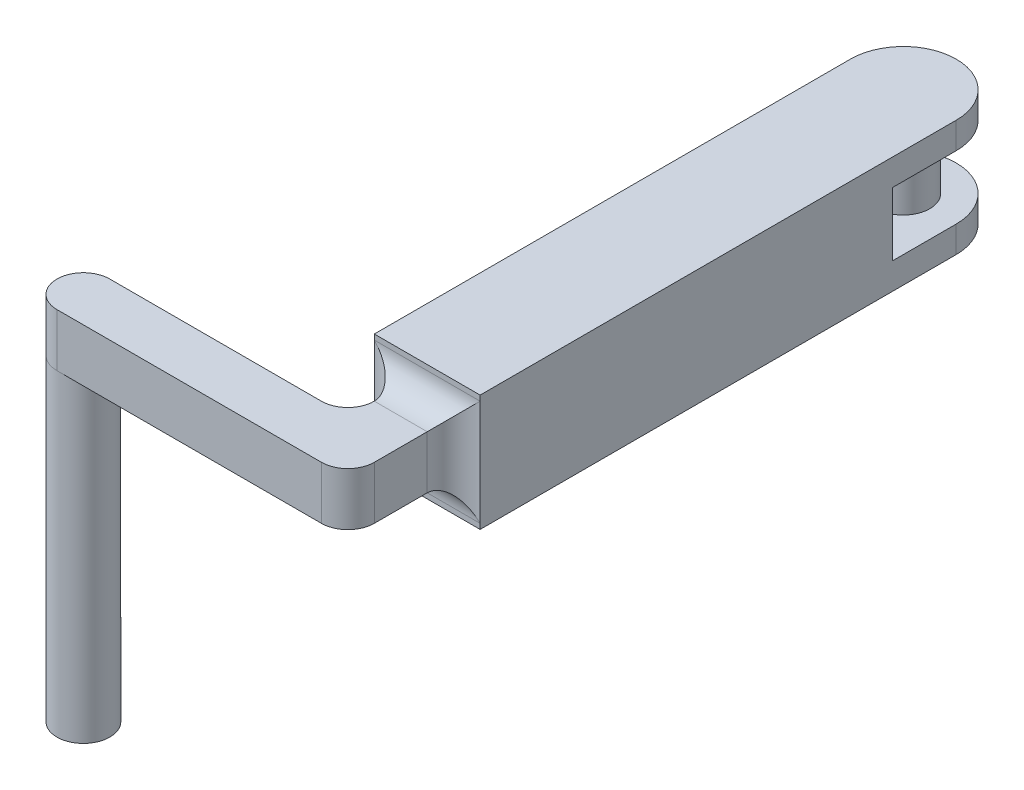
SolidWorks part; units mm, degrees
ref_plane "Front Plane" through (0, 0, 0) normal (0, 0, 1) x (1, 0, 0)
ref_plane "Top Plane" through (0, 0, 0) normal (0, 1, 0) x (1, 0, 0)
ref_plane "Right Plane" through (0, 0, 0) normal (1, 0, 0) x (0, 0, -1)
sketch "Sketch1" plane through (0, 0, 0) normal (0, 1, 0) x (1, 0, 0)
  circle A0 centre (0, 0) radius 3.175
  dimension "D1" = 6.35
extrude "Boss-Extrude1" add sketch "Sketch1" against normal blind 38.1
sketch "Sketch2" plane through (0, 0, 0) normal (0, 1, 0) x (1, 0, 0)
  line L0 (0, 0) -> (0, 3.175) construction
  line L1 (34.925, 3.175) -> (-3.175, 3.175) construction
  line L2 (34.925, 3.175) -> (34.925, -3.175) construction
  line L3 (34.925, -3.175) -> (-3.175, -3.175)
  line L4 (-3.175, 3.175) -> (-3.175, -3.175)
  line L5 (34.925, 3.175) -> (-3.175, -3.175) construction
  line L6 (34.925, -3.175) -> (-3.175, 3.175) construction
  line L7 (0, 0) -> (-3.175, 0) construction
  line L8 (-3.175, 3.175) -> (28.575, 3.175)
  line L9 (28.575, 3.175) -> (28.575, 60.325)
  line L10 (28.575, 60.325) -> (34.925, 60.325)
  line L11 (34.925, 60.325) -> (34.925, -3.175)
  point P0 (15.875, 0)
  dimension "D1" = 6.35
  dimension "D2" = 38.1
  dimension "D3" = 6.35
  dimension "D4" = 63.5
extrude "Boss-Extrude2" add sketch "Sketch2" along normal blind 6.35
fillet "Fillet1" radius 3.175 4 edges at (28.575, 3.175, -3.175) (34.925, 3.175, 3.175) (-3.175, 3.175, -3.175) (-3.175, 3.175, 3.175)
sketch "Sketch3" plane through (0, 6.35, 0) normal (0, 1, 0) x (1, 0, 0)
  line L0 (25.4, 41.275) -> (31.75, 41.275) construction
  line L1 (25.4, 9.525) -> (38.1, 9.525)
  line L2 (25.4, 9.525) -> (25.4, 73.025)
  line L3 (25.4, 73.025) -> (38.1, 73.025)
  line L4 (38.1, 9.525) -> (38.1, 73.025)
  line L5 (31.75, 41.275) -> (31.75, 73.025) construction
  line L6 (34.925, 60.325) -> (28.575, 60.325) construction
  line L7 (0, -3.175) -> (31.75, -3.175) construction
  point P9 (31.75, 60.325)
  dimension "D1" = 12.7
  dimension "D2" = 12.7
  dimension "D3" = 63.5
extrude "Boss-Extrude3" add sketch "Sketch3" against normal blind 10.16 and the other way blind 3.81
fillet "Fillet2" radius 3.175 4 edges at (28.575, 3.175, -9.525) (31.75, 0, -9.525) (34.925, 3.175, -9.525) (31.75, 6.35, -9.525)
fillet "Fillet3" radius 6.35 2 edges at (25.4, 3.175, -73.025) (38.1, 3.175, -73.025)
sketch "Sketch4" plane through (38.1, 0, 0) normal (1, 0, 0) x (0, 0, -1)
  line L0 (66.675, -3.81) -> (66.675, 10.16) construction
  line L1 (59.055, -0.635) -> (74.295, -0.635)
  line L2 (59.055, -0.635) -> (59.055, 6.985)
  line L3 (59.055, 6.985) -> (74.295, 6.985)
  line L4 (74.295, -0.635) -> (74.295, 6.985)
  line L5 (59.055, -0.635) -> (74.295, 6.985) construction
  line L6 (59.055, 6.985) -> (74.295, -0.635) construction
  line L7 (73.025, 10.16) -> (73.025, -3.81) construction
  point P0 (66.675, 3.175)
  dimension "D1" = 7.62
  dimension "D2" = 13.97
extrude "Cut-Extrude1" cut sketch "Sketch4" against normal up to next
sketch "Sketch5" plane through (0, -0.635, 0) normal (0, 1, 0) x (1, 0, 0)
  circle A0 centre (31.75, 66.675) radius 3.175
  arc A1 (31.75, 73.025) -> (25.4, 66.675) centre (31.75, 66.675) ccw construction
  dimension "D1" = 6.35
extrude "Boss-Extrude4" add sketch "Sketch5" along normal blind 10.16
